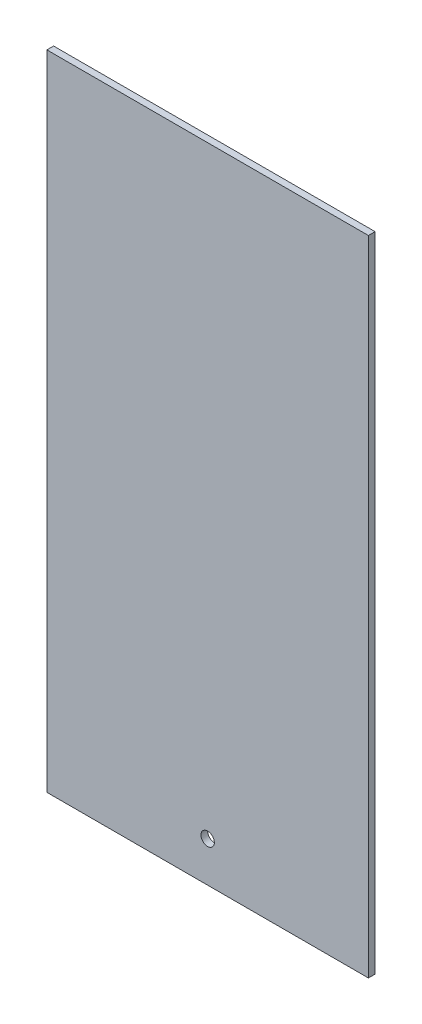
SolidWorks part; units mm, degrees
ref_plane "Front Plane" through (0, 0, 0) normal (0, 0, 1) x (1, 0, 0)
ref_plane "Top Plane" through (0, 0, 0) normal (0, 1, 0) x (1, 0, 0)
ref_plane "Right Plane" through (0, 0, 0) normal (1, 0, 0) x (0, 0, -1)
sketch "Sketch1" plane through (0, 0, 0) normal (0, 0, 1) x (1, 0, 0)
  line L1 (-76.2, -152.4) -> (76.2, -152.4)
  line L2 (-76.2, -152.4) -> (-76.2, 152.4)
  line L3 (-76.2, 152.4) -> (76.2, 152.4)
  line L4 (76.2, -152.4) -> (76.2, 152.4)
  line L5 (-76.2, -152.4) -> (76.2, 152.4) construction
  line L6 (-76.2, 152.4) -> (76.2, -152.4) construction
  point P0 (0, 0)
  dimension "D1" = 152.4
  dimension "D2" = 304.8
extrude "Boss-Extrude1" add sketch "Sketch1" along normal blind 3.175
sketch "Sketch2" plane through (0, 0, 3.175) normal (0, 0, 1) x (1, 0, 0)
  line L0 (-76.2, -152.4) -> (76.2, -152.4) construction
  circle A0 centre (0, -133.35) radius 3.175
  point P2 (0, 0)
  dimension "D1" = 6.35
  dimension "D2" = 19.05
extrude "Cut-Extrude1" cut sketch "Sketch2" against normal through all
